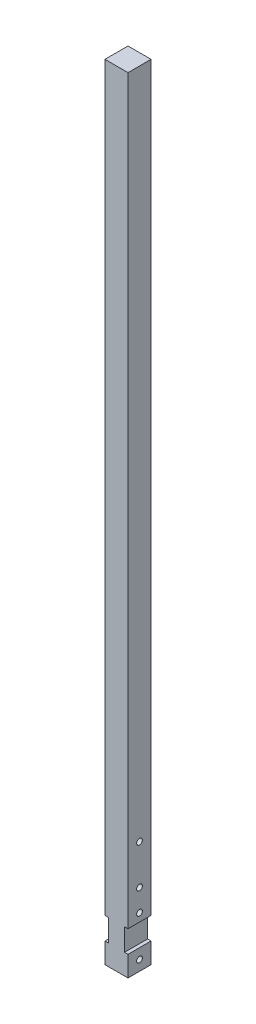
SolidWorks part; units mm, degrees
material "Alliage 1060"
ref_plane "Plan de face" through (0, 0, 0) normal (0, 0, 1) x (1, 0, 0)
ref_plane "Plan de dessus" through (0, 0, 0) normal (0, 1, 0) x (1, 0, 0)
ref_plane "Plan de droite" through (0, 0, 0) normal (1, 0, 0) x (0, 0, -1)
sketch "Esquisse1" plane through (0, 0, 0) normal (0, 1, 0) x (1, 0, 0)
  line L0 (-5, 5) -> (5, -5) construction
  line L1 (-5, 5) -> (5, 5)
  line L2 (-5, 5) -> (-5, -5)
  line L3 (-5, -5) -> (5, -5)
  line L4 (5, 5) -> (5, -5)
  dimension "D1" = 10
extrude "Boss.-Extru.1" add sketch "Esquisse1" along normal up to surface (340 mm away)
hole_wizard "Trou taraudé M3x0.51" positions "Esquisse2" profile "Esquisse3" tap size "M3x0.5" standard "Ansi Metric" end condition through all
sketch "Esquisse2" plane through (-5, 0, 0) normal (-1, 0, 0) x (0, 0, 1)
  line L0 (0, 50.3) -> (0, 47.1) construction
  line L1 (-2.6, 50.3) -> (2.9, 50.3) construction
  line L2 (2.9, 47.1) -> (-2.6, 47.1) construction
  line L6 (0, 33.1) -> (0, 29.9) construction
  line L7 (2.9, 29.9) -> (-2.6, 29.9) construction
  line L8 (-2.6, 33.1) -> (2.9, 33.1) construction
  circle A0 centre (0, 22) radius 3 construction
  circle A1 centre (0, 4.45) radius 3 construction
  point P0 (0, 22)
  point P3 (0, 4.45)
  point P6 (0, 31.5)
  point P8 (0, 48.7)
sketch "Esquisse3" plane through (-5, 22, 0) normal (0, 1, 0) x (0, 0, 1)
  line L0 (0, 0) -> (0, 10)
  line L1 (0, 10) -> (1.25, 10)
  line L2 (1.25, 10) -> (1.25, 0)
  line L5 (1.25, 0) -> (0, 0)
  line L11 (0, -6.35) -> (0, 107.95) construction
  dimension "Diamètre du trou pour taraudage jusqu'au prochain" = 2.5
  dimension "Profondeur du trou pour taraudage jusqu'au prochain" = 10
cosmetic thread "Filetage de perçage1" parameters "D2"=3
cosmetic thread "Filetage de perçage2" parameters "D2"=3
cosmetic thread "Filetage de perçage3" parameters "D2"=3
cosmetic thread "Filetage de perçage4" parameters "D2"=3
sketch "Esquisse4" plane through (0, 0, -5) normal (0, 0, -1) x (-1, 0, 0)
  line L0 (5, 340) -> (5, 0) construction
  line L1 (5, 18.5) -> (3.5, 18.5)
  line L2 (5, 18.5) -> (5, 8.9)
  line L3 (5, 8.9) -> (3.5, 8.9)
  line L4 (3.5, 18.5) -> (3.5, 8.9)
  line L5 (-3.5, 18.5) -> (-5, 18.5)
  line L6 (-3.5, 18.5) -> (-3.5, 8.9)
  line L7 (-3.5, 8.9) -> (-5, 8.9)
  line L8 (-5, 18.5) -> (-5, 8.9)
  line L9 (5, 18.5) -> (7.6438, 18.5) construction
  line L10 (5, 8.9) -> (8.1439, 8.9) construction
  line L11 (-5, 340) -> (-5, 0) construction
  dimension "D1" = 1.5
extrude "Enlèv. mat.-Extru.1" cut sketch "Esquisse4" against normal through all
